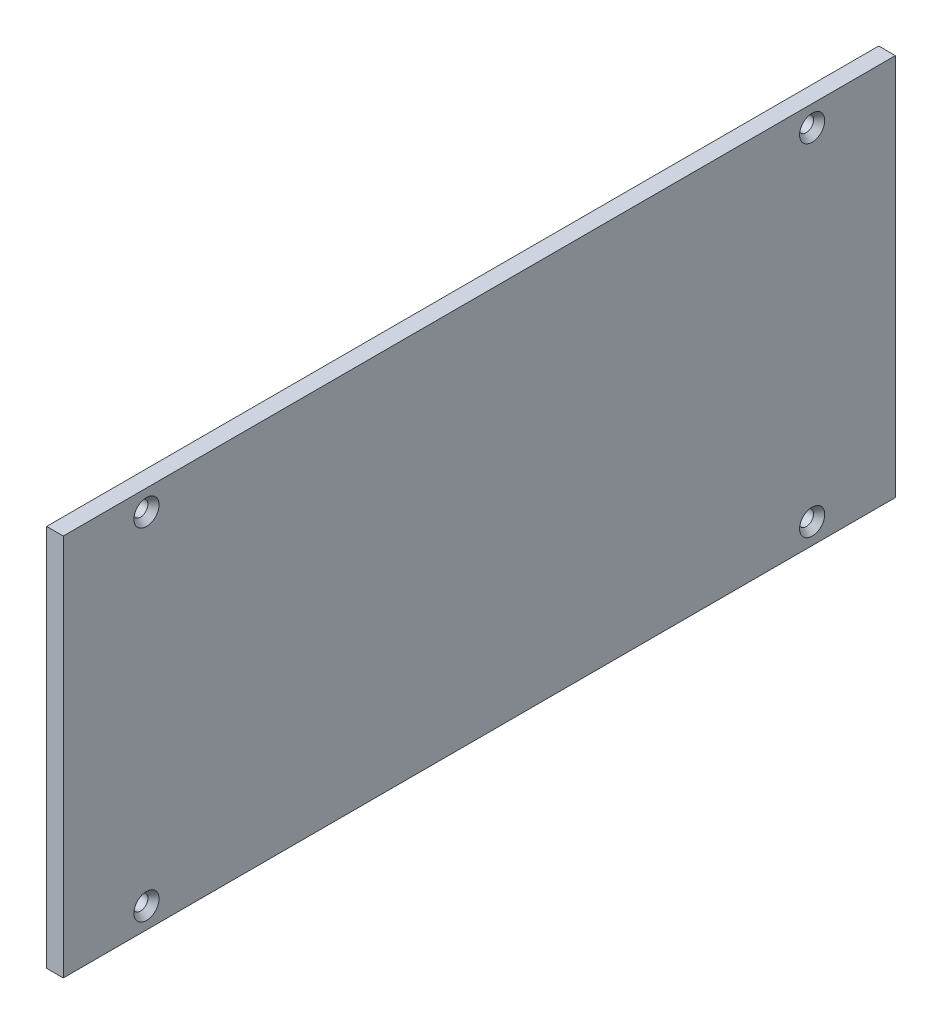
SolidWorks part; units mm, degrees
material "6061-T4 (SS)"
ref_plane "Front Plane" through (0, 0, 0) normal (0, 0, 1) x (1, 0, 0)
ref_plane "Top Plane" through (0, 0, 0) normal (0, 1, 0) x (1, 0, 0)
ref_plane "Right Plane" through (0, 0, 0) normal (1, 0, 0) x (0, 0, -1)
sketch "Sketch1" plane through (0, 0, 0) normal (1, 0, 0) x (0, 0, -1)
  line L1 (0, 0) -> (100, 0)
  line L2 (0, 0) -> (0, 46)
  line L3 (0, 46) -> (100, 46)
  line L4 (100, 0) -> (100, 46)
  dimension "D1" = 46
  dimension "D2" = 100
extrude "Boss-Extrude1" add sketch "Sketch1" along normal blind 2
hole_wizard "CSK for #0 Flat Head Machine Screw1" positions "Sketch3" profile "Sketch4" countersink size "#0" standard "ANSI Inch" end condition through all
sketch "Sketch3" plane through (2, 0, 0) normal (1, 0, 0) x (0, 0, -1)
  line L0 (10, 43.5) -> (10, 2.5) construction
  line L1 (10, 2.5) -> (90, 2.5) construction
  line L2 (90, 2.5) -> (90, 43.5) construction
  line L3 (90, 43.5) -> (10, 43.5) construction
  line L5 (0, 23) -> (10, 23) construction
  line L6 (0, 46) -> (0, 0) construction
  line L7 (10, 23) -> (90, 23) construction
  line L8 (90, 23) -> (100, 23) construction
  line L9 (100, 0) -> (100, 46) construction
  line L11 (100, 46) -> (0, 46) construction
  line L12 (0, 0) -> (100, 0) construction
  point P0 (10, 43.5)
  point P2 (10, 2.5)
  point P4 (90, 2.5)
  point P6 (90, 43.5)
  dimension "D1" = 10
  dimension "D2" = 2.5
  dimension "D3" = 2.5
  dimension "D4" = 10
sketch "Sketch4" plane through (2, 43.5, -10) normal (0, 1, 0) x (0, 0, -1)
  line L0 (0, 0) -> (0, 2)
  line L1 (0, 2) -> (0.889, 2)
  line L2 (0.889, 2) -> (0.889, 0.7159)
  line L3 (0.889, 0.7159) -> (1.5113, 0)
  line L5 (1.5113, 0) -> (0, 0)
  line L6 (-0.889, 0.7159) -> (-1.5113, 0) construction
  line L11 (0, -6.35) -> (0, 107.95) construction
  dimension "Thru Hole Dia." = 1.778
  dimension "Thru Hole Depth" = 2
  dimension "Near C'Sink Dia." = 3.0226
  dimension "Near C'Sink Angle" = 82
